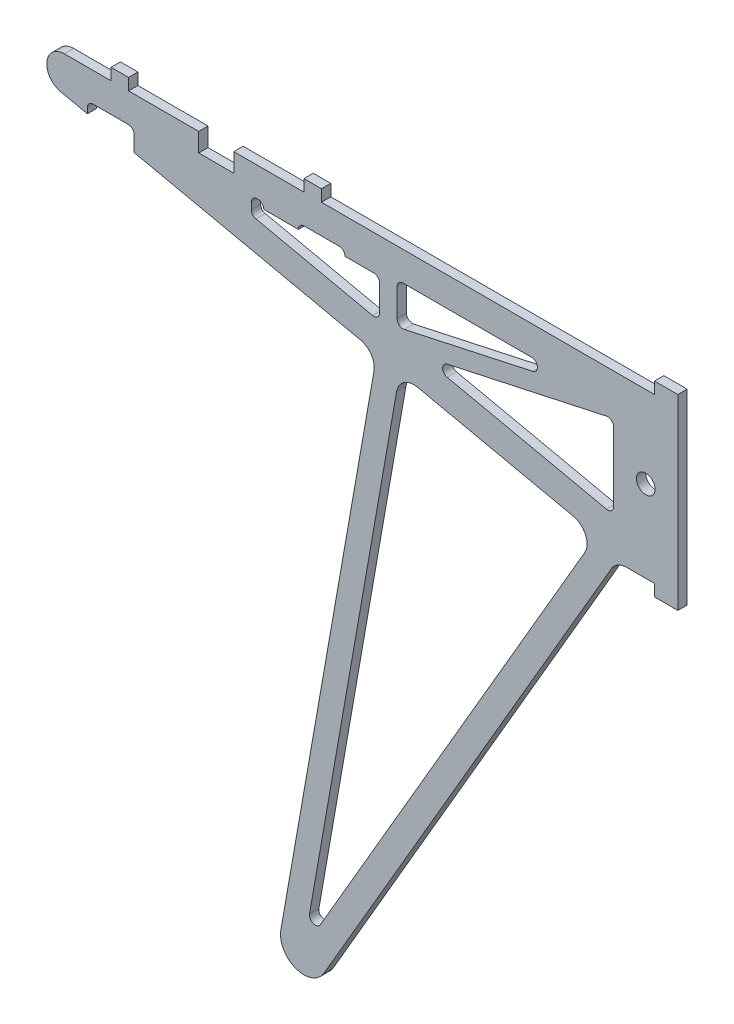
SolidWorks part; units mm, degrees
material "Thornel VCB-20 Carbon Cloth"
ref_plane "Front Plane" through (0, 0, 0) normal (0, 0, 1) x (1, 0, 0)
ref_plane "Top Plane" through (0, 0, 0) normal (0, 1, 0) x (1, 0, 0)
ref_plane "Right Plane" through (0, 0, 0) normal (1, 0, 0) x (0, 0, -1)
sketch "Sketch1" plane through (0, 0, 0) normal (0, 0, 1) x (1, 0, 0)
  line L0 (-21, 0) -> (-126, 0) construction
  line L1 (-126.6366, -5.9317) -> (-25, -28) construction
  line L2 (-25, -28) -> (-25, -30) construction
  line L3 (-25, -30) -> (-21, -30) construction
  line L4 (-21, -30) -> (-21, 0) construction
  line L5 (-118, 0) -> (-118, 2) construction
  line L6 (-118, 2) -> (-115, 2) construction
  line L7 (-115, 2) -> (-115, 0) construction
  line L8 (-85, 0) -> (-85, 2) construction
  line L9 (-85, 2) -> (-82, 2) construction
  line L10 (-82, 2) -> (-82, 0) construction
  line L11 (-25, 0) -> (-25, 2) construction
  line L12 (-25, 2) -> (-21, 2) construction
  line L13 (-21, 2) -> (-21, 0) construction
  line L14 (-25, 0) -> (-82, 0)
  line L15 (-126.6366, -5.9317) -> (-25, -28)
  line L16 (-25, -28) -> (-25, -30)
  line L17 (-25, -30) -> (-21, -30)
  line L18 (-21, -30) -> (-21, 0)
  line L19 (-118, 0) -> (-118, 2)
  line L20 (-118, 2) -> (-115, 2)
  line L21 (-115, 2) -> (-115, 0)
  line L22 (-85, 0) -> (-85, 2)
  line L23 (-85, 2) -> (-82, 2)
  line L24 (-82, 2) -> (-82, 0)
  line L25 (-25, 0) -> (-25, 2)
  line L26 (-25, 2) -> (-21, 2)
  line L27 (-21, 2) -> (-21, 0)
  line L28 (-118, 0) -> (-126, 0)
  line L29 (-85, 0) -> (-97, 0)
  line L30 (-107.3632, -5) -> (-32, -5)
  line L31 (-32, -5) -> (-32, -21.3636)
  line L32 (-32, -21.3636) -> (-107.3632, -5)
  line L33 (-69.6816, -13.1818) -> (-32, -5) construction
  line L34 (-69.6816, -13.1818) -> (-69.6816, -5) construction
  line L35 (-72.038, -12.6701) -> (-36.7129, -5)
  line L36 (-32, -7.0466) -> (-64.9687, -14.2051)
  line L37 (-72.038, -12.6701) -> (-72.038, -5)
  line L38 (-69.038, -5) -> (-69.038, -12.0188)
  line L39 (-103, 0) -> (-115, 0)
  line L41 (-103, 0) -> (-103, -3.2)
  line L42 (-103, -3.2) -> (-97, -3.2)
  line L43 (-97, 0) -> (-97, -3.2)
  arc A0 (-126, 0) -> (-126.6366, -5.9317) centre (-126, -3) ccw construction
  arc A1 (-126, 0) -> (-126.6366, -5.9317) centre (-126, -3) ccw
  dimension "D1" = 1
  dimension "D2" = 5
  dimension "D3" = 5
  dimension "D4" = 11
  dimension "D5" = 2
  dimension "D6" = 3
  dimension "D7" = 3
  dimension "D8" = 3
  dimension "D9" = 3.2
extrude "Boss-Extrude1" add sketch "Sketch1" along normal up to vertex (1.6 mm away) contours L28 A1 L15 L16 L17 L18 L27 L26 L25 L14 L24 L23 L22 L29 L21 L20 L19 L31 L32 L30 | L38 L30 L37 L35 | L36 L31 L30 L35 L32
sketch "Sketch2" plane through (0, 0, 1.6) normal (0, 0, 1) x (1, 0, 0)
  line L0 (-122.05, -5) -> (-114.05, -5)
  line L1 (-126.6366, -5.9317) -> (-25, -28) construction
  line L2 (-114.05, -5) -> (-114.05, -8.6646)
  line L3 (-114.05, -8.6646) -> (-122.05, -6.9276)
  line L4 (-122.05, -5) -> (-122.05, -6.9276)
  line L7 (-107.3632, -5) -> (-72.038, -5) construction
  line L8 (-118.05, -5) -> (-118.05, 2) construction
  line L9 (-116.45, 2) -> (-119.65, 2) construction
  dimension "D1" = 8
extrude "Cut-Extrude1" cut sketch "Sketch2" against normal up to next
sketch "Sketch3" plane through (0, 0, 1.6) normal (0, 0, 1) x (1, 0, 0)
  line L0 (-107.3632, -5) -> (-72.038, -5) construction
  line L1 (-77.95, -5) -> (-72.038, -5)
  line L2 (-77.95, -5) -> (-77.95, -6)
  line L3 (-77.95, -6) -> (-72.038, -6)
  line L4 (-72.038, -5) -> (-72.038, -6)
  line L5 (-72.038, -12.6701) -> (-72.038, -5) construction
  line L6 (-85.95, -5) -> (-77.95, -5) construction
  line L7 (-85.95, -5) -> (-91.862, -5)
  line L8 (-85.95, -5) -> (-85.95, -6)
  line L9 (-85.95, -6) -> (-91.862, -6)
  line L10 (-91.862, -5) -> (-91.862, -6)
  line L11 (-114.05, -5) -> (-122.05, -5) construction
  line L12 (-83.5, 2) -> (-81.95, -5) construction
  line L13 (-85, 2) -> (-82, 2) construction
  line L14 (-118.05, -5) -> (-116.5, 2) construction
  line L15 (-118, 2) -> (-115, 2) construction
  line L16 (-107.3632, -5) -> (-72.038, -5) construction
  dimension "D1" = 1
extrude "Boss-Extrude2" add sketch "Sketch3" against normal up to vertex (1.6 mm away)
sketch "Sketch4" plane through (0, 0, 1.6) normal (0, 0, 1) x (1, 0, 0)
  line L0 (-107.3632, -5) -> (-94, -5)
  line L1 (-107.3632, -5) -> (-91.862, -5) construction
  line L2 (-94, -5) -> (-94, -7.9015)
  line L3 (-72.038, -12.6701) -> (-107.3632, -5) construction
  line L4 (-94, -7.9015) -> (-107.3632, -5)
  line L5 (-97, 0) -> (-97, -3.2) construction
  dimension "D1" = 3
extrude "Boss-Extrude3" add sketch "Sketch4" against normal up to vertex (1.6 mm away)
fillet "Fillet2" radius 1 15 edges at (-64.9687, -14.2051, 0.8) (-69.038, -12.0188, 0.8) (-72.038, -12.6701, 0.8) (-69.038, -5, 0.8) (-36.7129, -5, 0.8) (-32, -7.0466, 0.8) (-32, -21.3636, 0.8) (-122.05, -5, 0.8) (-114.05, -5, 0.8) (-85.95, -5, 0.8) (-77.95, -5, 0.8) (-72.038, -6, 0.8) (-91.862, -5, 0.8) (-94, -7.9015, 0.8) (-94, -5, 0.8)
sketch "Sketch6" plane through (0, 0, 1.6) normal (0, 0, 1) x (1, 0, 0)
  line L0 (-32, -8.287) -> (-32, 0) construction
  line L1 (-25, 0) -> (-82, 0) construction
  line L2 (-32, 0) -> (-21, 0) construction
  line L3 (-21, -30) -> (-21, 2) construction
  line L4 (-26.5, 0) -> (-26.5, -14) construction
  line L6 (-21, -14) -> (-26.5, -14) construction
  circle A0 centre (-26.5, -14) radius 1.6
  dimension "D1" = 3.2
extrude "Cut-Extrude2" cut sketch "Sketch6" against normal through all
sketch "Sketch5" plane through (0, 0, 1.6) normal (0, 0, 1) x (1, 0, 0)
  line L0 (-72.5029, -17.6857) -> (-88.9397, -111.3083)
  line L1 (-114.05, -8.6646) -> (-25, -28) construction
  line L2 (-81.5426, -114.0116) -> (-31.5, -28)
  line L3 (-31.5, -28) -> (-25, -28)
  line L4 (-72.5029, -17.6857) -> (-68.5909, -18.5351)
  line L5 (-68.5909, -18.5351) -> (-84.0309, -106.48)
  line L6 (-34.8797, -25.8548) -> (-82.1816, -107.1558)
  line L7 (-34.8797, -25.8548) -> (-25, -28)
  line L8 (-70.5469, -18.1104) -> (-69.6816, -13.1818) construction
  arc A0 (-88.9397, -111.3083) -> (-81.5426, -114.0116) centre (-85, -112) ccw
  arc A1 (-82.1816, -107.1558) -> (-84.0309, -106.48) centre (-83.0459, -106.6529) cw
  dimension "D1" = 85
  dimension "D5" = 1
  dimension "D2" = 4
  dimension "D3" = 112
  dimension "D4" = 6.5
extrude "Boss-Extrude4" add sketch "Sketch5" against normal up to vertex (1.6 mm away)
fillet "Fillet3" radius 3 4 edges at (-31.5, -28, 0.8) (-34.8797, -25.8548, 0.8) (-68.5909, -18.5351, 0.8) (-72.5029, -17.6857, 0.8)
